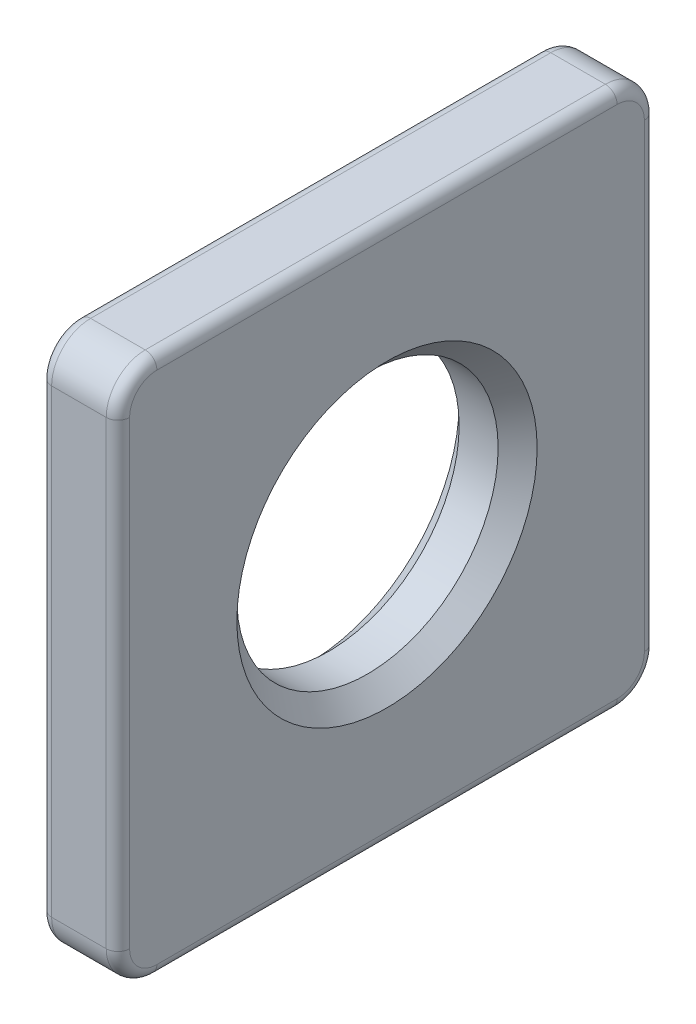
SolidWorks part; units mm, degrees
ref_plane "Front" through (0, 0, 0) normal (0, 0, 1) x (1, 0, 0)
ref_plane "Top" through (0, 0, 0) normal (0, 1, 0) x (1, 0, 0)
ref_plane "Right" through (0, 0, 0) normal (1, 0, 0) x (0, 0, -1)
sketch "Sketch1" plane through (0, 0, 0) normal (1, 0, 0) x (0, 0, -1)
  line L1 (6.9, -6.9) -> (-6.9, -6.9)
  line L2 (6.9, -6.9) -> (6.9, 6.9)
  line L3 (6.9, 6.9) -> (-6.9, 6.9)
  line L4 (-6.9, -6.9) -> (-6.9, 6.9)
  line L5 (6.9, -6.9) -> (-6.9, 6.9) construction
  line L6 (6.9, 6.9) -> (-6.9, -6.9) construction
  point P0 (0, 0)
  dimension "D1" = 6.9
  dimension "D2" = 13.8
extrude "Boss-Extrude1" add sketch "Sketch1" along normal blind 2
sketch "Sketch2" plane through (0, 0, 0) normal (1, 0, 0) x (0, 0, -1)
  circle A0 centre (0, 0) radius 3.35
  dimension "D1" = 6.7
extrude "Cut-Extrude1" cut sketch "Sketch2" along normal through all
chamfer "Chamfer1" distance 0.5 angle 45 2 edges at (0, 0, -3.35) (2, 0, -3.35)
fillet "Fillet1" radius 1 4 edges at (1, 6.9, -6.9) (1, -6.9, -6.9) (1, -6.9, 6.9) (1, 6.9, 6.9)
fillet "Fillet2" radius 0.3 16 edges at (0, 6.6071, 6.6071) (0, 6.9, 0) (0, 6.6071, -6.6071) (0, 0, -6.9) (0, -6.6071, -6.6071) (0, -6.9, 0) (0, -6.6071, 6.6071) (2, -6.6071, 6.6071) (2, 0, 6.9) (2, 6.6071, 6.6071) (2, 6.9, 0) (2, 6.6071, -6.6071) (2, 0, -6.9) (2, -6.6071, -6.6071) (0, 0, 6.9) (2, -6.9, 0)
equation "\"D2@Sketch1\"=2*\"D1@Sketch1\""
